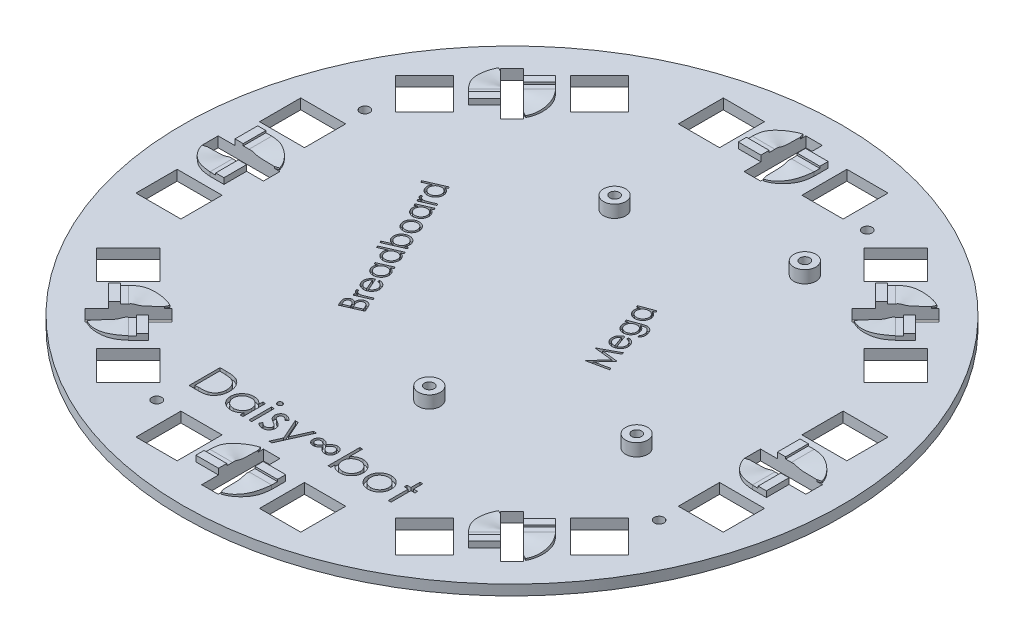
SolidWorks part; units mm, degrees
ref_plane "Front" through (0, 0, 0) normal (0, 0, 1) x (1, 0, 0)
ref_plane "Top" through (0, 0, 0) normal (0, 1, 0) x (1, 0, 0)
ref_plane "Right" through (0, 0, 0) normal (1, 0, 0) x (0, 0, -1)
sketch "Sketch1" plane through (0, 0, 0) normal (0, 1, 0) x (1, 0, 0)
  circle A0 centre (0, 0) radius 101.6
  dimension "D1" = 203.2
extrude "Boss-Extrude1" add sketch "Sketch1" along normal blind 3.175 contours A0
sketch "Sketch2" plane through (0, 3.175, 0) normal (0, 1, 0) x (1, 0, 0)
  line L1 (-2.54, -93.1333) -> (2.54, -93.1333)
  line L2 (-2.54, -93.1333) -> (-2.54, -74.0833)
  line L3 (-2.54, -74.0833) -> (2.54, -74.0833)
  line L4 (2.54, -93.1333) -> (2.54, -74.0833)
  point P4 (0, -74.0833)
  dimension "D1" = 5.08
  dimension "D2" = 19.05
  dimension "D3" = 93.1333
extrude "Cut-Extrude1" cut sketch "Sketch2" against normal up to next and the other way through all contours L1 L4 L3 L2
sketch "Sketch4" plane through (0, 3.175, 0) normal (0, 1, 0) x (1, 0, 0)
  line L0 (0, -83.6083) -> (-2.9434, -74.5495) construction
  line L1 (-2.9434, -74.5495) -> (0, -83.6083) construction
  line L2 (0, -83.6083) -> (-5.5987, -75.9024) construction
  line L3 (0, -83.6083) -> (-7.7059, -78.0097) construction
  line L4 (0, -83.6083) -> (-9.0588, -80.6649) construction
  line L5 (0, -83.6083) -> (-9.525, -83.6083) construction
  line L9 (2.54, -74.0833) -> (-2.54, -74.0833) construction
  line L10 (2.54, -74.0833) -> (2.54, -93.1333) construction
  line L11 (-2.54, -74.0833) -> (-2.54, -93.1333) construction
  line L12 (2.54, -93.1333) -> (-2.54, -93.1333) construction
  circle A0 centre (0, -83.6083) radius 9.525 construction
  point P16 (0, -74.0833)
  point P19 (2.54, -83.6083)
  dimension "D1" = 18
  dimension "D2" = 18
  dimension "D3" = 18
  dimension "D4" = 18
  dimension "D5" = 18
ref_plane "Plane1" through (-24.5719, 0, 7.9839) normal (0.9511, 0, -0.309) x (-0.309, 0, -0.9511)
ref_plane "Plane2" through (-39.7581, 0, 28.886) normal (0.809, 0, -0.5878) x (-0.5878, 0, -0.809)
ref_plane "Plane3" through (-39.7581, 0, 54.7224) normal (0.5878, 0, -0.809) x (-0.809, 0, -0.5878)
ref_plane "Plane4" through (-24.5719, 0, 75.6244) normal (0.309, 0, -0.9511) x (-0.9511, 0, -0.309)
ref_plane "Plane5" through (0, 0, 83.6083) normal (0, 0, -1) x (-1, 0, 0)
sketch "Sketch5" plane through (-24.5719, 0, 7.9839) normal (0.9511, 0, -0.309) x (-0.309, 0, -0.9511)
  line L0 (-69.6725, 3.175) -> (-87.7902, 3.175) construction
  line L1 (-71.2966, 3.175) -> (-69.9913, 3.175)
  line L2 (-71.2966, 3.175) -> (-71.2966, 3.683)
  line L3 (-71.2966, 3.683) -> (-69.9913, 3.683)
  line L4 (-69.9913, 3.175) -> (-69.9913, 3.683)
  dimension "D2" = 0.508
sketch "Sketch6" plane through (-39.7581, 0, 28.886) normal (0.809, 0, -0.5878) x (-0.5878, 0, -0.809)
  line L0 (-58.4417, 3.175) -> (-73.8535, 3.175) construction
  line L1 (-63.3193, 3.175) -> (-58.1156, 3.175)
  line L2 (-63.3193, 3.175) -> (-63.3193, 3.775)
  line L3 (-63.3193, 3.775) -> (-58.1156, 3.775)
  line L4 (-58.1156, 3.175) -> (-58.1156, 3.775)
  dimension "D2" = 0.6
sketch "Sketch7" plane through (-39.7581, 0, 54.7224) normal (0.5878, 0, -0.809) x (-0.809, 0, -0.5878)
  line L0 (-41.4902, 3.175) -> (-52.6875, 3.175) construction
  line L1 (-46.0041, 3.175) -> (-39.6187, 3.175)
  line L2 (-46.0041, 3.175) -> (-46.0041, 4.075)
  line L3 (-46.0041, 4.075) -> (-39.6187, 4.075)
  line L4 (-39.6187, 3.175) -> (-39.6187, 4.075)
  dimension "D2" = 0.9
sketch "Sketch10" plane through (-24.5719, 0, 75.6244) normal (0.309, 0, -0.9511) x (-0.9511, 0, -0.309)
  line L0 (-25.8364, 3.175) -> (-16.7776, 3.175) construction
  line L1 (-23.1657, 3.175) -> (-16.3114, 3.175)
  line L2 (-23.1657, 3.175) -> (-23.1657, 4.375)
  line L3 (-23.1657, 4.375) -> (-16.3114, 4.375)
  line L4 (-16.3114, 3.175) -> (-16.3114, 4.375)
  dimension "D3" = 1.2
sketch "Sketch11" plane through (0, 0, 83.6083) normal (0, 0, -1) x (-1, 0, 0)
  line L0 (0, 3.175) -> (9.525, 3.175) construction
  line L1 (2.54, 3.175) -> (9.525, 3.175)
  line L2 (2.54, 3.175) -> (2.54, 4.375)
  line L3 (2.54, 4.375) -> (9.525, 4.375)
  line L4 (9.525, 3.175) -> (9.525, 4.375)
  dimension "D3" = 1.2
loft "Loft1" add profiles "Sketch5", "Sketch6", "Sketch7", "Sketch10", "Sketch11" connector at (-2.54, 3.683, 75.791) connector at (-2.54, 3.775, 80.1123) connector at (-2.54, 4.075, 81.7629) connector at (-2.54, 4.375, 82.783) connector at (-2.54, 4.375, 83.6083)
sketch "Sketch13" plane through (-104.9799, 0, 83.6083) normal (0, 0, -1) x (-1, 0, 0)
  line L6 (-95.4549, 3.175) -> (-102.4399, 3.175)
  line L7 (-95.4549, 3.175) -> (-95.4549, 4.375)
  line L8 (-95.4549, 4.375) -> (-102.4399, 4.375)
  line L9 (-102.4399, 3.175) -> (-102.4399, 4.375)
extrude "Boss-Extrude4" add sketch "Sketch13" against normal blind 1.7907
sketch "Sketch25" plane through (0, 0, 85.399) normal (0, 0, 1) x (1, 0, 0)
  line L0 (-9.525, 4.375) -> (-2.54, 4.375) construction
  line L1 (-9.525, 3.175) -> (-2.54, 3.175)
  line L2 (-9.525, 3.175) -> (-9.525, 4.975)
  line L3 (-9.525, 4.975) -> (-2.54, 4.975)
  line L4 (-2.54, 3.175) -> (-2.54, 4.975)
  dimension "D1" = 0.6
extrude "Boss-Extrude5" add sketch "Sketch25" along normal blind 2.54
sketch "Sketch14" plane through (-2.54, 0, 0) normal (1, 0, 0) x (0, 0, -1)
  line L0 (-83.6083, 3.175) -> (-83.6083, 0) construction
  line L1 (-74.0833, 0) -> (-93.1333, 0) construction
ref_plane "Plane6" through (0, 0, 0) normal (1, 0, 0) x (0, 0, -1)
sketch "Sketch15" plane through (0, 0, 0) normal (1, 0, 0) x (0, 0, -1)
  line L0 (-83.6083, 0) -> (-83.6083, 3.175) construction
pattern_circular "CirPattern1" count 2 over 360 about axis through (0, 0, 83.6083) along (0, 1, 0) of "Loft1", "Boss-Extrude5", "Boss-Extrude4" reverse direction yes
ref_axis "Axis1" through (0, 50, 0) along (0, -1, 0)
pattern_circular "CirPattern5" count 8 over 360 about axis through (0, 50, 0) along (0, -1, 0) of "CirPattern1", "Cut-Extrude1"
sketch "Sketch18" plane through (0, 3.175, 0) normal (0, 1, 0) x (1, 0, 0)
  line L0 (-12.3739, 44.0137) -> (34.085, 57.075) construction
  line L1 (-12.3739, 44.0137) -> (9.9679, -35.4555) construction
  line L2 (34.085, 57.075) -> (34.4287, 55.8524) construction
  line L3 (54.7082, -16.2811) -> (8.2493, -29.3425) construction
  line L4 (0, -101.6) -> (0, 101.6) construction
  line L5 (0, -1.7463) -> (0, 1.7463) construction
  line L6 (-101.6, 0) -> (101.6, 0) construction
  line L7 (34.4287, 55.8524) -> (54.7082, -16.2811) construction
  circle A0 centre (-12.3739, 44.0137) radius 3.405
  circle A1 centre (9.9679, -35.4555) radius 3.405
  circle A2 centre (54.7082, -16.2811) radius 3.405
  circle A3 centre (34.4287, 55.8524) radius 3.405
  circle A4 centre (9.9679, -35.4555) radius 1.5
  circle A5 centre (-12.3739, 44.0137) radius 1.5
  circle A6 centre (34.4287, 55.8524) radius 1.5
  circle A7 centre (54.7082, -16.2811) radius 1.5
  circle A8 centre (0, 0) radius 101.6 construction
  dimension "D7" = 1.905
  dimension "D8" = 3
  dimension "D9" = 1.27
  dimension "D1" = 82.55
  dimension "D2" = 74.93
  dimension "D4" = 15.703
  dimension "D5" = 36.83
  dimension "D10" = 48.26
sketch "Sketch19" plane through (0, 3.175, 0) normal (0, 1, 0) x (1, 0, 0)
  line L0 (-32.0765, -77.4396) -> (0, 0) construction
  line L1 (0, -101.6) -> (0, 101.6) construction
  circle A1 centre (-32.0765, -77.4396) radius 1.5
  circle A4 centre (0, 0) radius 101.6 construction
  dimension "D4" = 3
  dimension "D6" = 83.82
  dimension "D5" = 22.5
extrude "Cut-Extrude2" cut sketch "Sketch19" against normal through all
pattern_circular "CirPattern7" count 4 over 360 about axis through (0, 50, 0) along (0, -1, 0) of "Cut-Extrude2"
extrude "Boss-Extrude3" add sketch "Sketch18" along normal blind 3.81
sketch "Sketch23" plane through (0, 3.175, 0) normal (0, 1, 0) x (1, 0, 0)
  line L9 (-2.54, -87.939) -> (-2.54, -93.1333) construction
  line L10 (-25.4, -76.6805) -> (-12.7, -76.6805)
  line L11 (-25.4, -76.6805) -> (-25.4, -90.5362)
  line L16 (-25.4, -90.5362) -> (-12.7, -90.5362)
  line L17 (-12.7, -76.6805) -> (-12.7, -90.5362)
  line L19 (2.54, -74.0833) -> (2.54, -79.2776) construction
  line L20 (0, -50) -> (0, 50) construction
  line L21 (12.7, -76.6805) -> (12.7, -90.5362)
  line L22 (25.4, -90.5362) -> (12.7, -90.5362)
  line L23 (25.4, -76.6805) -> (25.4, -90.5362)
  line L24 (25.4, -76.6805) -> (12.7, -76.6805)
  point P8 (-2.54, -90.5362)
  point P9 (2.54, -76.6805)
  dimension "D1" = 12.7
  dimension "D2" = 10.16
extrude "Cut-Extrude6" cut sketch "Sketch23" against normal through all
pattern_circular "CirPattern8" count 8 over 360 about axis through (0, 50, 0) along (0, -1, 0) of "Cut-Extrude6"
sketch "Sketch17" plane through (0, 3.175, 0) normal (0, 1, 0) x (1, 0, 0)
  line L0 (33.02, -68.58) -> (-33.02, -68.58) construction
  line L1 (2.54, -74.0833) -> (-2.54, -74.0833) construction
  point P2 (63.1398, -28.708)
  point P3 (0, -68.58)
  point P5 (24.2634, -74.5244)
  point P7 (0, -74.0833)
  point P8 (0, 0)
  point P9 (0, 0)
  dimension "D2" = 68.58
  dimension "D1" = 66.04
sketch "Sketch16" plane through (0, 3.175, 0) normal (0, 1, 0) x (1, 0, 0)
  line L0 (33.02, -68.58) -> (-33.02, -68.58) construction
  text T0 "Daisy∞bot\r\n" font "Century Gothic" height in points 36
  point P1 (0, 0)
  point P2 (0, 0)
  point P3 (0, -61.6662)
extrude "Cut-Extrude4" cut sketch "Sketch16" against normal blind 1.27
sketch "Sketch22" plane through (0, 3.175, 0) normal (0, 1, 0) x (1, 0, 0)
  line L0 (-44.1287, 25.1735) -> (-20.5694, -28.6741) construction
  text T0 "Breadboard"
extrude "Cut-Extrude5" cut sketch "Sketch22" against normal blind 1.27
sketch "Sketch24" plane through (0, 3.175, 0) normal (0, 1, 0) x (1, 0, 0)
  line L0 (29.8571, 0) -> (21.0896, 23.8389) construction
  text T0 "Mega"
  dimension "D1" = 28.022
  dimension "D2" = 25.4
  dimension "D3" = 29.8571
extrude "Cut-Extrude7" cut sketch "Sketch24" against normal blind 1.27
